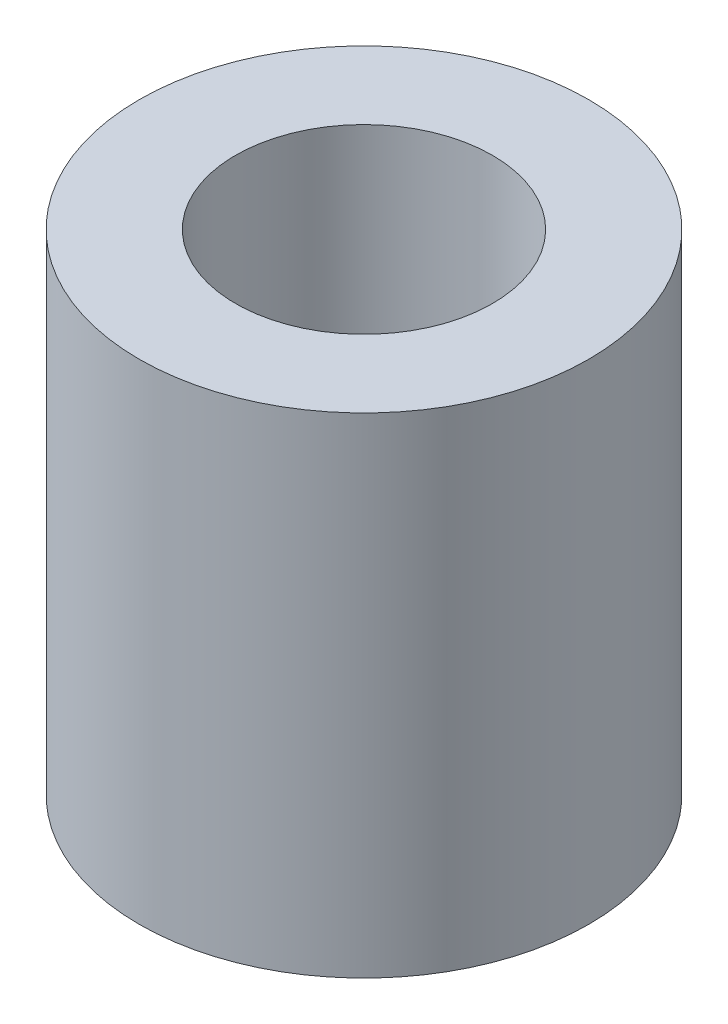
SolidWorks part; units mm, degrees
material "HTPB"
ref_plane "Front Plane" through (0, 0, 0) normal (0, 0, 1) x (1, 0, 0)
ref_plane "Top Plane" through (0, 0, 0) normal (0, 1, 0) x (1, 0, 0)
ref_plane "Right Plane" through (0, 0, 0) normal (1, 0, 0) x (0, 0, -1)
sketch "Sketch1" plane through (0, 0, 0) normal (0, 1, 0) x (1, 0, 0)
  circle A0 centre (0, 0) radius 20
  circle A1 centre (0, 0) radius 35
  dimension "D1" = 40
  dimension "D2" = 70
extrude "Boss-Extrude1" add sketch "Sketch1" along normal blind 76.2
